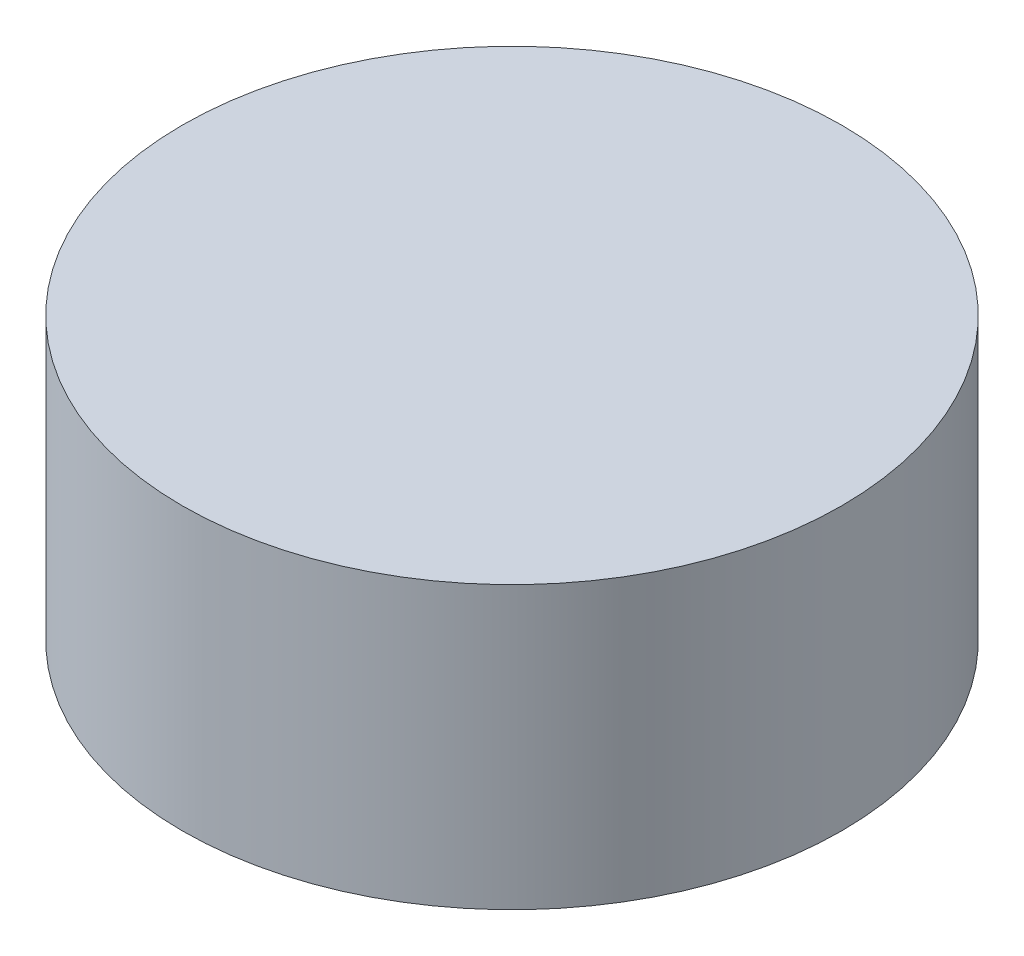
SolidWorks part; units mm, degrees
ref_plane "Front Plane" through (0, 0, 0) normal (0, 0, 1) x (1, 0, 0)
ref_plane "Top Plane" through (0, 0, 0) normal (0, 1, 0) x (1, 0, 0)
ref_plane "Right Plane" through (0, 0, 0) normal (1, 0, 0) x (0, 0, -1)
sketch "Sketch1" plane through (0, 0, 0) normal (0, 1, 0) x (1, 0, 0)
  circle A0 centre (0, 0) radius 44.5
  dimension "D1" = 89
extrude "Boss-Extrude1" add sketch "Sketch1" along normal blind 38
